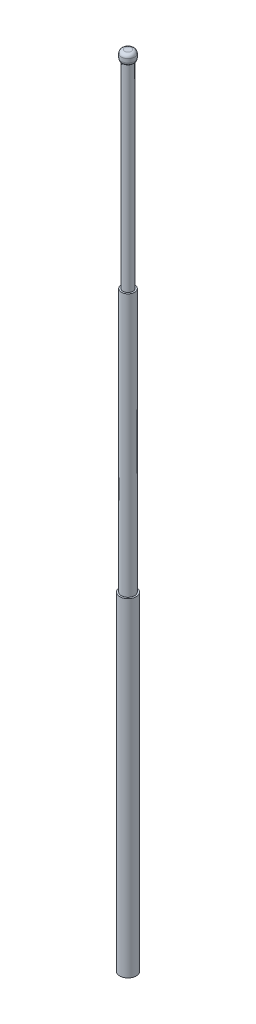
SolidWorks part; units mm, degrees
ref_plane "Front Plane" through (0, 0, 0) normal (0, 0, 1) x (1, 0, 0)
ref_plane "Top Plane" through (0, 0, 0) normal (0, 1, 0) x (1, 0, 0)
ref_plane "Right Plane" through (0, 0, 0) normal (1, 0, 0) x (0, 0, -1)
sketch "Sketch1" plane through (0, 0, 0) normal (0, 1, 0) x (1, 0, 0)
  circle A0 centre (0, 0) radius 6.35
  dimension "D1" = 12.7
extrude "Boss-Extrude1" add sketch "Sketch1" along normal blind 254
sketch "Sketch2" plane through (0, 254, 0) normal (0, 1, 0) x (1, 0, 0)
  circle A0 centre (0, 0) radius 5.08
  dimension "D1" = 10.16
extrude "Boss-Extrude2" add sketch "Sketch2" along normal blind 203.2
sketch "Sketch3" plane through (0, 457.2, 0) normal (0, 1, 0) x (1, 0, 0)
  circle A0 centre (0, 0) radius 3.81
  dimension "D1" = 7.62
extrude "Boss-Extrude3" add sketch "Sketch3" along normal blind 152.4
sketch "Sketch4" plane through (0, 609.6, 0) normal (0, 1, 0) x (1, 0, 0)
  circle A0 centre (0, 0) radius 5.08
  dimension "D1" = 10.16
extrude "Boss-Extrude4" add sketch "Sketch4" along normal blind 7.62
fillet "Fillet1" radius 2.54 2 edges at (0, 617.22, 5.08) (0, 609.6, 5.08)
